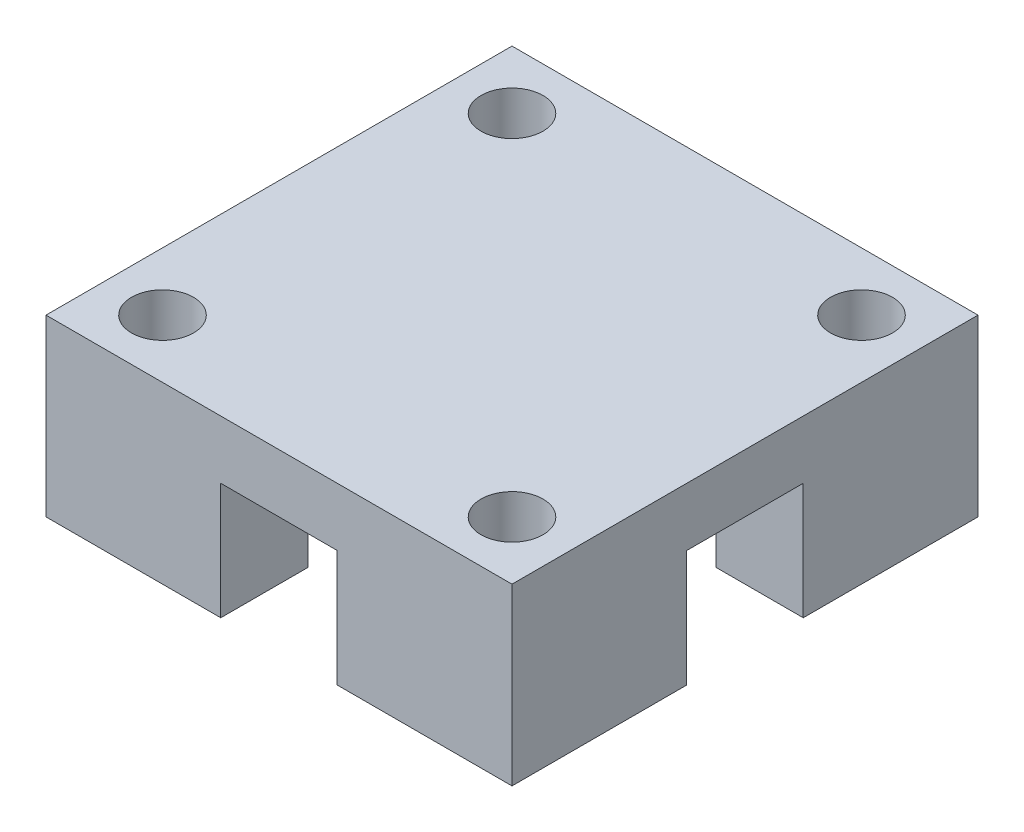
SolidWorks part; units mm, degrees
ref_plane "Front Plane" through (0, 0, 0) normal (0, 0, 1) x (1, 0, 0)
ref_plane "Top Plane" through (0, 0, 0) normal (0, 1, 0) x (1, 0, 0)
ref_plane "Right Plane" through (0, 0, 0) normal (1, 0, 0) x (0, 0, -1)
sketch "Sketch1" plane through (0, 0, 0) normal (0, 1, 0) x (1, 0, 0)
  line L1 (-25.4, 25.4) -> (25.4, 25.4)
  line L2 (-25.4, 25.4) -> (-25.4, -25.4)
  line L3 (-25.4, -25.4) -> (25.4, -25.4)
  line L4 (25.4, 25.4) -> (25.4, -25.4)
  line L5 (-25.4, 25.4) -> (25.4, -25.4) construction
  line L6 (-25.4, -25.4) -> (25.4, 25.4) construction
  point P0 (0, 0)
  dimension "D1" = 50.8
  dimension "D2" = 50.8
extrude "Boss-Extrude1" add sketch "Sketch1" along normal blind 19.05
hole_wizard "1/4 Clearance Hole1" positions "Sketch8" profile "Sketch7" hole size "1/4" standard "ANSI Inch" end condition through all
sketch "Sketch8" plane through (0, 19.05, 0) normal (0, 1, 0) x (1, 0, 0)
  point P0 (-19.05, 19.05)
  point P2 (19.05, 19.05)
  point P4 (19.05, -19.05)
  point P6 (-19.05, -19.05)
sketch "Sketch7" plane through (-19.05, 19.05, -19.05) normal (1, 0, 0) x (0, 0, 1)
  line L0 (0, 0) -> (0, 19.05)
  line L1 (0, 19.05) -> (3.3782, 19.05)
  line L2 (3.3782, 19.05) -> (3.3782, 0)
  line L5 (3.3782, 0) -> (0, 0)
  line L11 (0, -6.35) -> (0, 107.95) construction
  dimension "Thru Hole Dia." = 6.7564
  dimension "Thru Hole Depth" = 19.05
sketch "Sketch9" plane through (0, 0, 0) normal (0, -1, 0) x (1, 0, 0)
  line L0 (-25.4, 25.4) -> (25.4, 25.4) construction
  line L1 (-6.35, 25.4) -> (6.35, 25.4)
  line L2 (-6.35, 25.4) -> (-6.35, -25.4)
  line L3 (-6.35, -25.4) -> (6.35, -25.4)
  line L4 (6.35, 25.4) -> (6.35, -25.4)
  line L5 (25.4, -25.4) -> (-25.4, -25.4) construction
  line L6 (-25.4, -25.4) -> (-25.4, 25.4) construction
  line L7 (-25.4, 6.35) -> (25.4, 6.35)
  line L8 (-25.4, 6.35) -> (-25.4, -6.35)
  line L9 (-25.4, -6.35) -> (25.4, -6.35)
  line L10 (25.4, 6.35) -> (25.4, -6.35)
  line L11 (25.4, 25.4) -> (25.4, -25.4) construction
  line L13 (-15.875, 15.875) -> (15.875, 15.875)
  line L14 (-15.875, 15.875) -> (-15.875, -15.875)
  line L15 (-15.875, -15.875) -> (15.875, -15.875)
  line L16 (15.875, 15.875) -> (15.875, -15.875)
  line L17 (-15.875, 15.875) -> (15.875, -15.875) construction
  line L18 (-15.875, -15.875) -> (15.875, 15.875) construction
  point P17 (0, 0)
  dimension "D1" = 12.7
  dimension "D2" = 6.35
  dimension "D3" = 12.7
  dimension "D4" = 6.35
  dimension "D5" = 31.75
  dimension "D6" = 31.75
extrude "Cut-Extrude1" cut sketch "Sketch9" against normal blind 12.7 contours L13 L16 L15 L14 | L2 L3 L4 L1 | L9 L10 L7 L8
